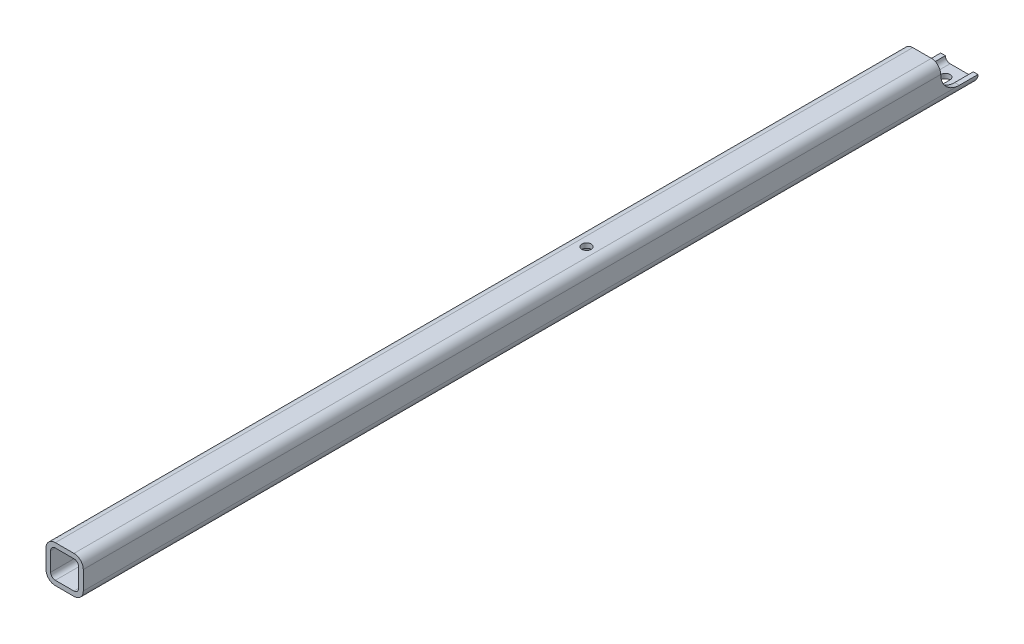
SolidWorks part; units mm, degrees
ref_plane "Front Plane" through (0, 0, 0) normal (0, 0, 1) x (1, 0, 0)
ref_plane "Top Plane" through (0, 0, 0) normal (0, 1, 0) x (1, 0, 0)
ref_plane "Right Plane" through (0, 0, 0) normal (1, 0, 0) x (0, 0, -1)
sketch "Sketch1" plane through (0, 0, 0) normal (0, 0, 1) x (1, 0, 0)
  line L0 (12.7, 6.35) -> (38.1, 6.35)
  line L1 (6.35, 12.7) -> (6.35, 38.1)
  line L2 (38.1, 44.45) -> (12.7, 44.45)
  line L3 (44.45, 38.1) -> (44.45, 12.7)
  line L4 (12.7, 0) -> (38.1, 0)
  line L5 (0, 12.7) -> (0, 38.1)
  line L6 (38.1, 50.8) -> (12.7, 50.8)
  line L7 (50.8, 38.1) -> (50.8, 12.7)
  arc A0 (50.8, 38.1) -> (38.1, 50.8) centre (38.1, 38.1) ccw
  arc A1 (38.1, 0) -> (50.8, 12.7) centre (38.1, 12.7) ccw
  arc A2 (0, 12.7) -> (12.7, 0) centre (12.7, 12.7) ccw
  arc A3 (12.7, 50.8) -> (0, 38.1) centre (12.7, 38.1) ccw
  arc A4 (12.7, 44.45) -> (6.35, 38.1) centre (12.7, 38.1) ccw
  arc A5 (44.45, 38.1) -> (38.1, 44.45) centre (38.1, 38.1) ccw
  arc A6 (38.1, 6.35) -> (44.45, 12.7) centre (38.1, 12.7) ccw
  arc A7 (6.35, 12.7) -> (12.7, 6.35) centre (12.7, 12.7) ccw
  dimension "D1" = 12.7
  dimension "Thickness" = 6.35
  dimension "V_leg" = 50.8
  dimension "H_leg" = 50.8
extrude "Boss-Extrude1" add sketch "Sketch1" along normal mid plane 1219.2
hole_wizard "1/2 (0.5) Diameter Hole1" positions "Sketch3" profile "Sketch4" hole size "1/2" standard "Ansi Inch" end condition through all
sketch "Sketch3" plane through (0, 50.8, 0) normal (0, 1, 0) x (-1, 0, 0)
  line L1 (0, 609.6) -> (0, -609.6) construction
  line L2 (-38.1, -609.6) -> (-12.7, -609.6) construction
  point P0 (-25.4, -101.6)
  dimension "D1" = 508
  dimension "D2" = 25.4
sketch "Sketch4" plane through (25.4, 50.8, -101.6) normal (1, 0, 0) x (0, 0, 1)
  line L0 (0, 0) -> (0, 50.8)
  line L1 (0, 50.8) -> (6.35, 50.8)
  line L2 (6.35, 50.8) -> (6.35, 0)
  line L5 (6.35, 0) -> (0, 0)
  line L11 (0, -6.35) -> (0, 107.95) construction
  dimension "Thru Hole Dia." = 12.7
  dimension "Thru Hole Depth" = 50.8
sketch "Sketch8" plane through (50.8, 0, 0) normal (1, 0, 0) x (0, 0, -1)
  line L1 (609.6, 12.7) -> (609.6, 38.1) construction
  line L2 (558.8, 50.8) -> (609.6, 50.8)
  line L3 (609.6, 50.8) -> (609.6, 12.7)
  line L4 (-609.6, 50.8) -> (609.6, 50.8) construction
  line L5 (609.6, 12.7) -> (558.8, 12.7)
  line L6 (-609.6, 12.7) -> (609.6, 12.7) construction
  line L7 (558.8, 12.7) -> (558.8, 50.8)
  dimension "D1" = 38.1
  dimension "D2" = 50.8
extrude "Cut-Extrude2" cut sketch "Sketch8" against normal through all
sketch "Sketch9" plane through (0, 0, 0) normal (0, -1, 0) x (1, 0, 0)
  line L0 (25.4, -590.55) -> (25.4, -571.5) construction
  line L1 (19.05, -590.55) -> (19.05, -571.5)
  line L2 (31.75, -590.55) -> (31.75, -571.5)
  line L3 (12.7, -609.6) -> (38.1, -609.6) construction
  line L4 (25.4, -609.6) -> (25.4, -590.55) construction
  arc A0 (19.05, -590.55) -> (31.75, -590.55) centre (25.4, -590.55) ccw
  arc A1 (31.75, -571.5) -> (19.05, -571.5) centre (25.4, -571.5) ccw
  point P2 (25.4, -581.025)
  dimension "D2" = 6.35
  dimension "D1" = 19.05
  dimension "D3" = 19.05
extrude "Cut-Extrude3" cut sketch "Sketch9" against normal up to next
fillet "Fillet1" radius 25.4 2 edges at (3.175, 12.7, -558.8) (47.625, 12.7, -558.8)
